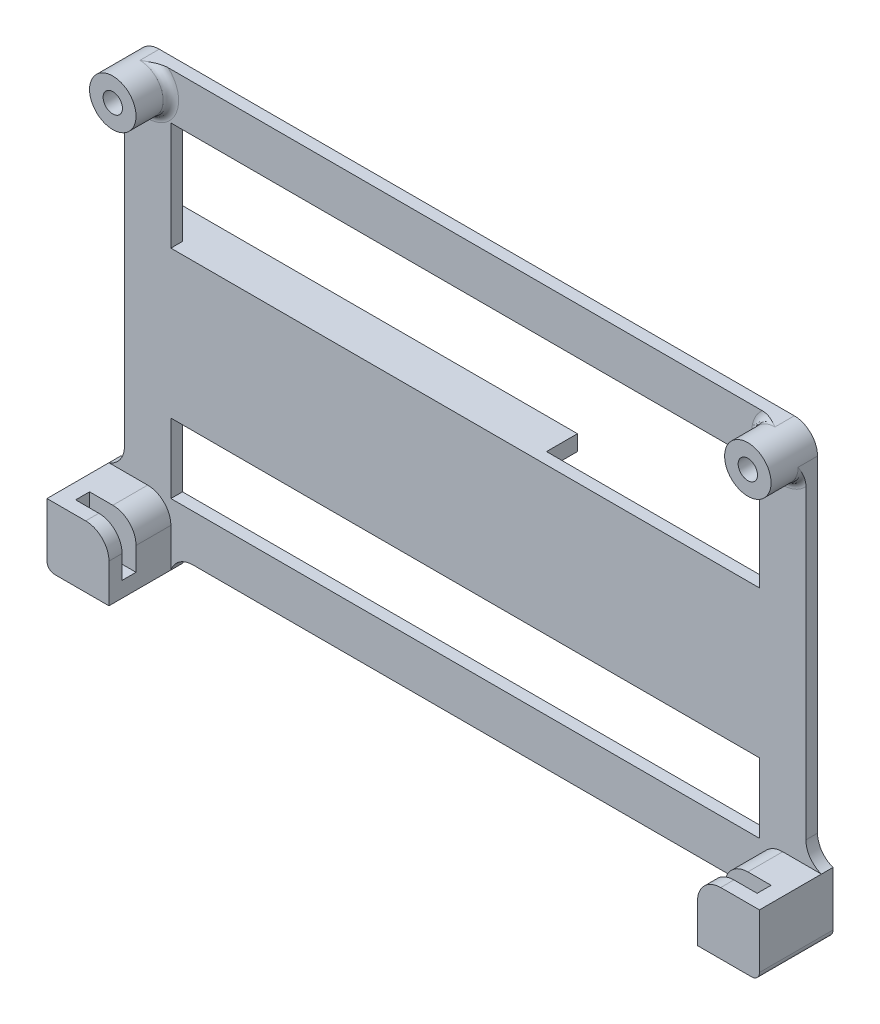
SolidWorks part; units mm, degrees
ref_plane "Front Plane" through (0, 0, 0) normal (0, 0, 1) x (1, 0, 0)
ref_plane "Top Plane" through (0, 0, 0) normal (0, 1, 0) x (1, 0, 0)
ref_plane "Right Plane" through (0, 0, 0) normal (1, 0, 0) x (0, 0, -1)
sketch "Sketch1" plane through (0, 0, 0) normal (0, 0, 1) x (1, 0, 0)
  line L0 (0, 0) -> (0, 29.6863) construction
  line L1 (0, 0) -> (50.0896, 0) construction
  line L2 (-44, 27) -> (44, 27)
  line L3 (44, 27) -> (44, -27)
  line L4 (-44, -27) -> (44, -27)
  line L5 (-44, 27) -> (-44, -27)
  line L6 (41, -21) -> (44, -21)
  line L7 (-38, 21) -> (38, 21)
  line L8 (-38, 21) -> (-38, -21)
  line L9 (-38, -21) -> (38, -21)
  line L10 (38, 21) -> (38, -21)
  line L11 (38, -24) -> (38, -27)
  line L12 (-41, -21) -> (-44, -21)
  line L13 (-38, -24) -> (-38, -27)
  line L14 (-38, -27) -> (-38, -29)
  line L15 (-38, -29) -> (-46, -29)
  line L16 (-46, -29) -> (-46, -21)
  line L17 (-46, -21) -> (-44, -21)
  line L18 (44, -21) -> (46, -21)
  line L19 (46, -21) -> (46, -29)
  line L20 (46, -29) -> (38, -29)
  line L21 (38, -29) -> (38, -27)
  circle A0 centre (41, 24) radius 1.25
  circle A1 centre (41, -24) radius 1.25
  circle A2 centre (-41, 24) radius 1.25
  circle A3 centre (-41, -24) radius 1.25
  circle A4 centre (41, -24) radius 3
  circle A5 centre (41, 24) radius 3
  circle A6 centre (-41, 24) radius 3
  circle A7 centre (-41, -24) radius 3
  point P10 (44, 0)
  point P14 (0, 27)
  point P19 (0, -27)
  dimension "D3" = 2.5
  dimension "D1" = 41
  dimension "D2" = 24
  dimension "D4" = 3
  dimension "D5" = 3
  dimension "D6" = 6
  dimension "D7" = 6
  dimension "D8" = 6
  dimension "D9" = 6
  dimension "D10" = 2
  dimension "D11" = 2
  dimension "D12" = 2
  dimension "D13" = 2
extrude "Boss-Extrude1" add sketch "Sketch1" along normal blind 1.5 contours A7 L13 L4 L11 A4 L6 L3 A5 L2 A6 L5 L12 L7 L10 L9 L8 region at (0, 25.9675, 0)
extrude "Boss-Extrude2" add sketch "Sketch1<3>" along normal blind 6 contours A5 A0 | A6 A2 | A4 L11 L4 | A4 A1 | A4 L3 L6 | A4 L4 L3 | A7 L12 L5 | A7 A3 | A7 L5 L4 | A7 L4 L13 | A3 | A1 region at (-38.9387, 26.0613, 0) region at (43.0613, 26.0613, 0) region at (-43.3299, -21.6701, 0) region at (-43.3299, -26.3299, 0) region at (-43.0613, -21.9387, 0) region at (43.3299, -21.6701, 0) region at (-38.6701, -26.3299, 0) region at (43.0613, -26.0613, 0) region at (43.3299, -26.3299, 0) region at (38.6701, -26.3299, 0)
sketch "Sketch1<3>" plane through (0, 0, 0) normal (0, 0, 1) x (1, 0, 0) same geometry as "Sketch1"
extrude "Boss-Extrude3" add sketch "Sketch1<4>" along normal blind 9.5 contours L21 L20 L19 L18 L3 L4 | L17 L16 L15 L14 L4 L5 region at (-44.1131, -22.5, 0) region at (45, -21.1131, 0)
sketch "Sketch1<4>" plane through (0, 0, 0) normal (0, 0, 1) x (1, 0, 0) same geometry as "Sketch1"
extrude "Boss-Extrude4" add sketch "Sketch1<5>" along normal blind 1.7 from offset 7.8 contours A3 | A7 A3 | A7 L5 L4 | A7 L4 L13 | A7 L12 L5 | A1 | A4 A1 | A4 L3 L6 | A4 L4 L3 | A4 L11 L4 region at (-43.3299, -21.6701, 0) region at (-43.3299, -26.3299, 0) region at (-43.0613, -21.9387, 0) region at (43.3299, -21.6701, 0) region at (-38.6701, -26.3299, 0) region at (43.0613, -26.0613, 0) region at (43.3299, -26.3299, 0) region at (38.6701, -26.3299, 0) region at (41, -24, 0) region at (-41, -24, 0)
sketch "Sketch1<5>" plane through (0, 0, 0) normal (0, 0, 1) x (1, 0, 0) same geometry as "Sketch1"
fillet "Fillet2" radius 3 4 edges at (44, -21, 0.75) (38, -27, 0.75) (-38, -27, 0.75) (-44, -21, 0.75)
fillet "Fillet1" radius 1 4 edges at (46, -29, 4.75) (-46, -29, 4.75) (-44, -27, 6.9) (44, -27, 6.9)
sketch "Sketch2" plane through (0, 0, 1.5) normal (0, 0, 1) x (1, 0, 0)
  line L0 (-38, 21) -> (-38, -21) construction
  line L1 (-38, 7) -> (38, 7)
  line L2 (-38, 7) -> (-38, -12)
  line L3 (-38, -12) -> (38, -12)
  line L4 (38, 7) -> (38, -12)
  line L5 (38, 21) -> (38, -21) construction
  line L6 (-38, -29) -> (-45, -29) construction
  line L7 (45, -29) -> (38, -29) construction
  dimension "D1" = 17
  dimension "D2" = 36
extrude "Boss-Extrude5" add sketch "Sketch2" against normal blind 1.5
sketch "Sketch3" plane through (0, 0, 0) normal (0, 0, -1) x (-1, 0, 0)
  line L0 (-38, 7) -> (38, 7) construction
  line L1 (-9, 7) -> (44, 7)
  line L2 (-9, 7) -> (-9, 5)
  line L3 (-9, 5) -> (44, 5)
  line L4 (44, 7) -> (44, 5)
  line L5 (44, 24) -> (44, -18.1716) construction
  line L6 (38, -12) -> (-38, -12) construction
  line L7 (-9, -12) -> (44, -12)
  line L8 (-9, -12) -> (-9, -10)
  line L9 (-9, -10) -> (44, -10)
  line L10 (44, -12) -> (44, -10)
  line L11 (-46, -21) -> (-46, -28) construction
  dimension "D1" = 2
  dimension "D2" = 37
  dimension "D3" = 2
  dimension "D4" = 37
extrude "Boss-Extrude6" add sketch "Sketch3" along normal blind 4
fillet "Fillet3" radius 1 2 edges at (38.8787, 21.8787, 1.5) (-38.8787, 21.8787, 1.5)
